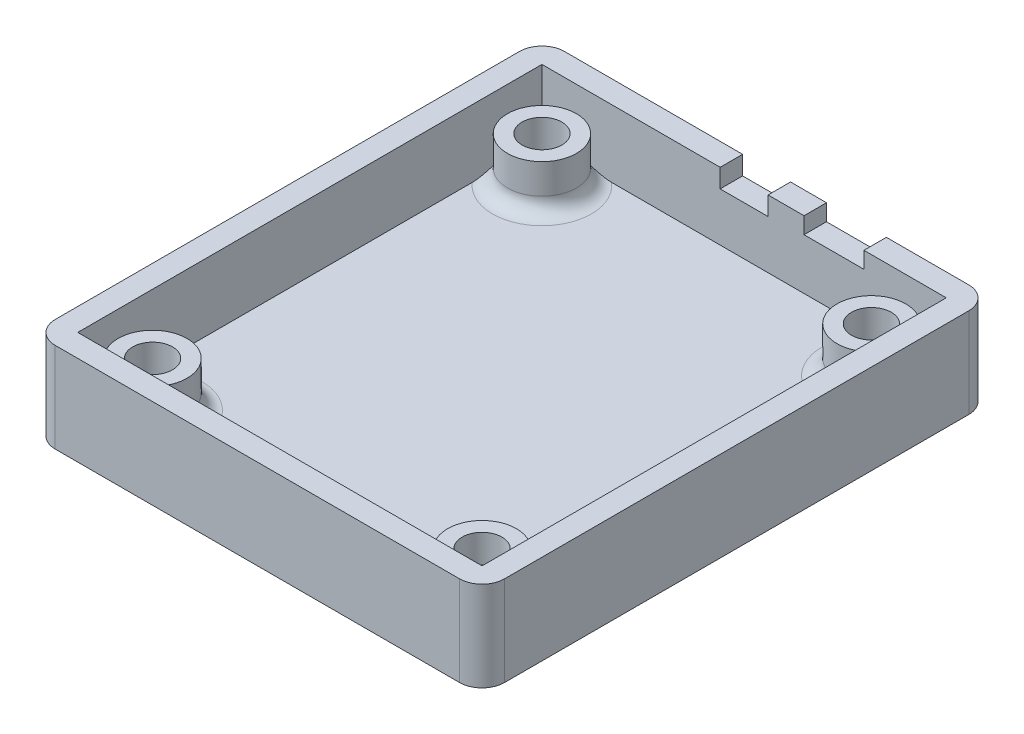
SolidWorks part; units mm, degrees
ref_plane "Front Plane" through (0, 0, 0) normal (0, 0, 1) x (1, 0, 0)
ref_plane "Top Plane" through (0, 0, 0) normal (0, 1, 0) x (1, 0, 0)
ref_plane "Right Plane" through (0, 0, 0) normal (1, 0, 0) x (0, 0, -1)
sketch "Sketch3" plane through (0, 0, 0) normal (0, 1, 0) x (1, 0, 0)
  line L1 (0, 0) -> (76.2, 0)
  line L2 (0, 0) -> (0, 86.36)
  line L3 (0, 86.36) -> (76.2, 86.36)
  line L4 (76.2, 0) -> (76.2, 86.36)
  dimension "D1" = 76.2
  dimension "D2" = 86.36
extrude "Boss-Extrude2" add sketch "Sketch3" along normal blind 15.24
sketch "Sketch6" plane through (0, 15.24, 0) normal (0, 1, 0) x (1, 0, 0)
  line L1 (0, 86.36) -> (0, 0) construction
  line L2 (3.81, 82.55) -> (72.39, 82.55)
  line L3 (3.81, 82.55) -> (3.81, 3.81)
  line L4 (3.81, 3.81) -> (72.39, 3.81)
  line L5 (72.39, 82.55) -> (72.39, 3.81)
  line L6 (76.2, 86.36) -> (0, 86.36) construction
  dimension "D1" = 68.58
  dimension "D2" = 78.74
  dimension "D3" = 3.81
  dimension "D4" = 3.81
extrude "Cut-Extrude2" cut sketch "Sketch6" against normal blind 11.43
sketch "Sketch7" plane through (0, 3.81, 0) normal (0, 1, 0) x (1, 0, 0)
  line L0 (3.81, 82.55) -> (3.81, 3.81) construction
  line L1 (72.39, 82.55) -> (3.81, 82.55) construction
  line L2 (72.39, 3.81) -> (72.39, 82.55) construction
  line L3 (3.81, 3.81) -> (72.39, 3.81) construction
  circle A0 centre (10.16, 76.2) radius 3.302
  circle A1 centre (66.04, 76.2) radius 3.302
  circle A2 centre (66.04, 10.16) radius 3.302
  circle A3 centre (10.16, 10.16) radius 3.302
  circle A4 centre (10.16, 76.2) radius 5.842
  circle A5 centre (66.04, 76.2) radius 5.842
  circle A6 centre (10.16, 10.16) radius 5.842
  circle A7 centre (66.04, 10.16) radius 5.842
  dimension "D3" = 6.604
  dimension "D1" = 6.35
  dimension "D2" = 6.35
  dimension "D4" = 6.35
  dimension "D5" = 6.35
  dimension "D6" = 2.54
extrude "Boss-Extrude3" add sketch "Sketch7" along normal blind 7.62
fillet "Fillet1" radius 2.54 4 edges at (66.04, 3.81, -4.318) (10.16, 3.81, -4.318) (66.04, 3.81, -70.358) (10.16, 3.81, -70.358)
hole_wizard "CSK for 1/4 Flat Head Machine Screw (100)1" positions "Sketch9" profile "Sketch10" countersink size "1/4" standard "ANSI Inch"
sketch "Sketch9" plane through (0, 0, 0) normal (0, -1, 0) x (-1, 0, 0)
  point P0 (-10.16, 10.16)
  point P3 (-66.04, 10.16)
  point P6 (-66.04, 76.2)
  point P9 (-10.16, 76.2)
sketch "Sketch10" plane through (10.16, 0, -10.16) normal (1, 0, 0) x (0, 0, -1)
  line L0 (0, 0) -> (0, 93.4698)
  line L1 (0, 93.4698) -> (3.3782, 91.44)
  line L2 (3.3782, 91.44) -> (3.3782, 2.5682)
  line L3 (3.3782, 2.5682) -> (6.4389, 0)
  line L5 (6.4389, 0) -> (0, 0)
  line L6 (-3.3782, 2.5682) -> (-6.4389, 0) construction
  line L10 (0, 93.4698) -> (-3.3782, 91.44) construction
  line L11 (0, -6.35) -> (0, 107.95) construction
  dimension "Hole Dia." = 6.7564
  dimension "Hole Depth" = 91.44
  dimension "Near C'Sink Dia." = 12.8778
  dimension "Near C'Sink Angle" = 100
  dimension "Drill Angle" = 118
sketch "Sketch11" plane through (0, 0, -86.36) normal (0, 0, -1) x (-1, 0, 0)
  line L0 (-76.2, 15.24) -> (0, 15.24) construction
  line L1 (-42.164, 15.24) -> (-34.036, 15.24)
  line L2 (-42.164, 15.24) -> (-42.164, 12.065)
  line L3 (-42.164, 12.065) -> (-34.036, 12.065)
  line L4 (-34.036, 15.24) -> (-34.036, 12.065)
  line L5 (-76.2, 15.24) -> (-76.2, 0) construction
  point P6 (-38.1, 15.24)
  dimension "D1" = 8.128
  dimension "D2" = 3.175
  dimension "D3" = 38.1
extrude "Cut-Extrude4" cut sketch "Sketch11" against normal up to next
sketch "Sketch12" plane through (0, 0, -86.36) normal (0, 0, -1) x (-1, 0, 0)
  line L0 (-76.2, 15.24) -> (-42.164, 15.24) construction
  line L1 (-58.42, 15.24) -> (-48.26, 15.24)
  line L2 (-58.42, 15.24) -> (-58.42, 12.446)
  line L3 (-58.42, 12.446) -> (-48.26, 12.446)
  line L4 (-48.26, 15.24) -> (-48.26, 12.446)
  line L5 (-76.2, 15.24) -> (-76.2, 0) construction
  dimension "D1" = 17.78
  dimension "D2" = 10.16
  dimension "D3" = 2.794
extrude "Cut-Extrude5" cut sketch "Sketch12" against normal up to next
fillet "Fillet2" radius 3.81 4 edges at (76.2, 7.62, -86.36) (0, 7.62, -86.36) (0, 7.62, 0) (76.2, 7.62, 0)
equation "\"D3@Sketch6\"=(\"D1@Sketch3\"-\"D1@Sketch6\")/2"
equation "\"D4@Sketch6\"=(3.4-3.1)/2"
